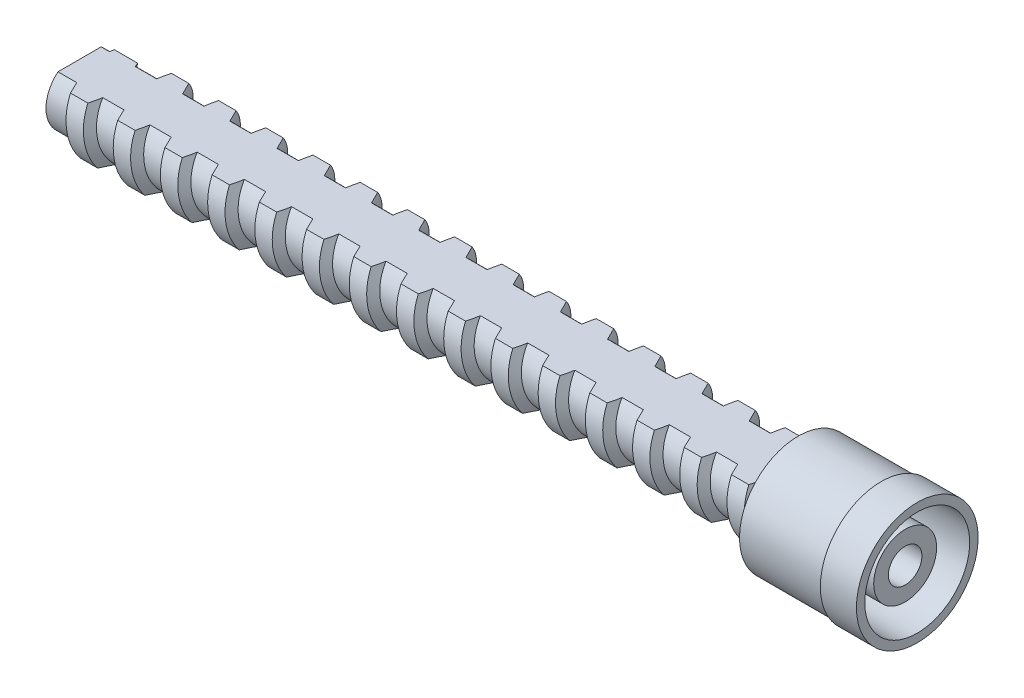
SolidWorks part; units mm, degrees
ref_plane "Plano frontal" through (0, 0, 0) normal (0, 0, 1) x (1, 0, 0)
ref_plane "Plano superior" through (0, 0, 0) normal (0, 1, 0) x (1, 0, 0)
ref_plane "Plano direito" through (0, 0, 0) normal (1, 0, 0) x (0, 0, -1)
sketch "Esboço1" plane through (0, 0, 0) normal (0, 0, 1) x (1, 0, 0)
  line L0 (0, 0) -> (7.4591, 0) construction
  line L1 (0, 1.6) -> (34.25, 1.6)
  line L2 (34.25, 1.6) -> (34.25, 2.8)
  line L3 (34.25, 2.8) -> (38.202, 2.8)
  line L4 (38.202, 2.8) -> (38.202, 2.9)
  line L5 (38.202, 2.9) -> (39.9215, 2.9)
  line L6 (39.9215, 2.9) -> (39.9215, 2.5)
  line L7 (39.9215, 2.5) -> (34.5707, 2.5)
  line L8 (34.5707, 2.5) -> (34.5707, 1.5)
  line L9 (34.5707, 1.5) -> (39.3442, 1.5)
  line L10 (39.3442, 1.5) -> (39.3442, 0.8)
  line L11 (39.3442, 0.8) -> (35.3609, 0.8)
  line L12 (0, 1.6) -> (0, 0)
  line L13 (0, 0) -> (35.3609, 0)
  line L14 (35.3609, 0) -> (35.3609, 0.8)
  dimension "D1" = 1.6
  dimension "D2" = 34.25
  dimension "D3" = 5.6
  dimension "D4" = 0.4
  dimension "D5" = 1
  dimension "D6" = 0.7
revolve "Revolução1" add sketch "Esboço1" angle 360 about L0
sketch "Esboço2" plane through (0, 0, 0) normal (1, 0, 0) x (0, 0, -1)
  line L0 (0, 0) -> (1.2264, 0) construction
  line L1 (2.4902, -1.225) -> (-2.2774, -1.225)
  line L2 (2.4902, -1.225) -> (2.4902, 1.225)
  line L3 (2.4902, 1.225) -> (-2.2774, 1.225)
  line L4 (-2.2774, -1.225) -> (-2.2774, 1.225)
  dimension "D1" = 2.45
sketch "Esboço3" plane through (0, 0, 0) normal (-1, 0, 0) x (0, 0, 1)
  circle A0 centre (0, 0) radius 1.6
curve "Hélice/Espiral1" pitch 2.25 height 33.75 turns 15
sketch "Esboço5" plane through (0, 0, 0) normal (0, 1, 0) x (1, 0, 0)
  line L0 (1.1972, -1.5759) -> (1.4083, -2.0226)
  line L1 (1.4083, -2.0226) -> (2.2361, -2.0226)
  line L2 (2.2361, -2.0226) -> (2.4472, -1.599)
  line L4 (2.4472, -1.599) -> (2.4472, -1.2402)
  line L5 (2.4472, -1.2402) -> (1.1972, -1.2402)
  line L6 (1.1972, -1.2402) -> (1.1972, -1.5759)
  line L7 (1.8222, -2.0226) -> (1.8222, -1.0371) construction
  dimension "D1" = 1.25
sweep "Varredura2" add profiles "Esboço5" path "Hélice/Espiral1"
sketch "Esboço6" plane through (0, 0, 0) normal (1, 0, 0) x (0, 0, -1)
  line L0 (-2.2774, -1.225) -> (-2.2774, 1.225) construction
  line L1 (2.4902, 1.225) -> (-2.2774, 1.225) construction
  line L2 (2.4902, -1.225) -> (-2.2774, -1.225) construction
  line L3 (2.4902, -1.225) -> (2.4902, 1.225) construction
  line L4 (-2.2774, -1.225) -> (-2.2774, 1.225)
  line L5 (2.4902, 1.225) -> (-2.2774, 1.225)
  line L6 (2.4902, -1.225) -> (-2.2774, -1.225)
  line L7 (2.4902, -1.225) -> (2.4902, 1.225)
extrude "Corte-extrusão2" cut sketch "Esboço6" along normal up to surface (34.25 mm away) flip side to cut up to face at (34.25, 0.2274, -0.5149)
